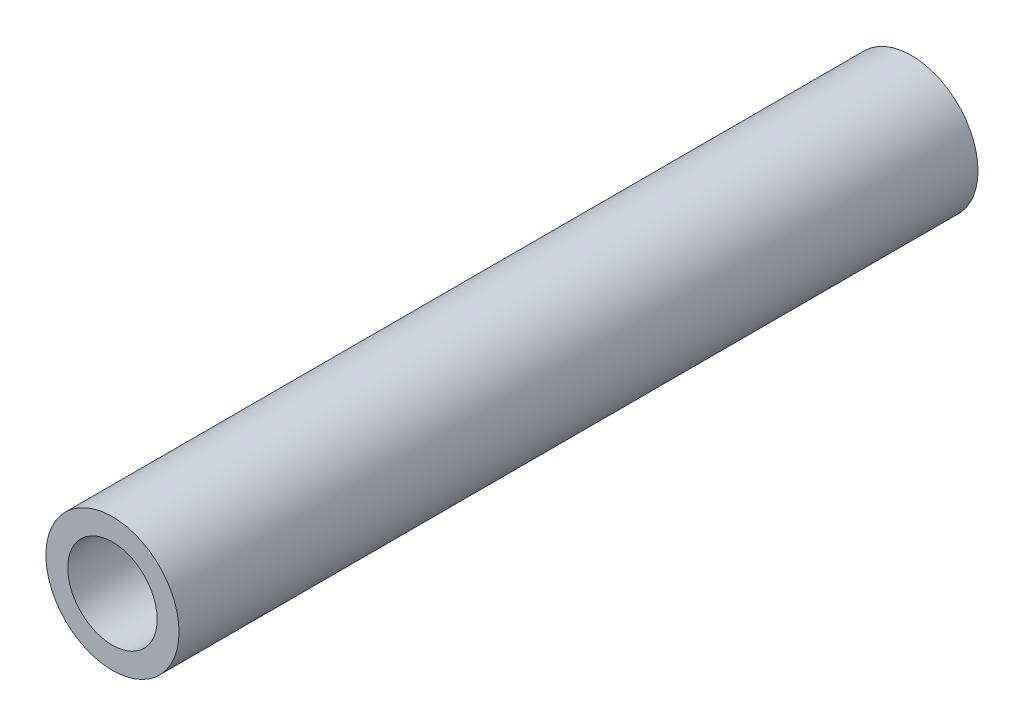
SolidWorks part; units mm, degrees
ref_plane "Спереди" through (0, 0, 0) normal (0, 0, 1) x (1, 0, 0)
ref_plane "Сверху" through (0, 0, 0) normal (0, 1, 0) x (1, 0, 0)
ref_plane "Справа" through (0, 0, 0) normal (1, 0, 0) x (0, 0, -1)
sketch "Эскиз1" plane through (0, 0, 0) normal (0, 0, 1) x (1, 0, 0)
  circle A0 centre (0, 0) radius 4.2
  circle A1 centre (0, 0) radius 6.25
extrude "Бобышка-Вытянуть1" add sketch "Эскиз1" along normal blind 75
